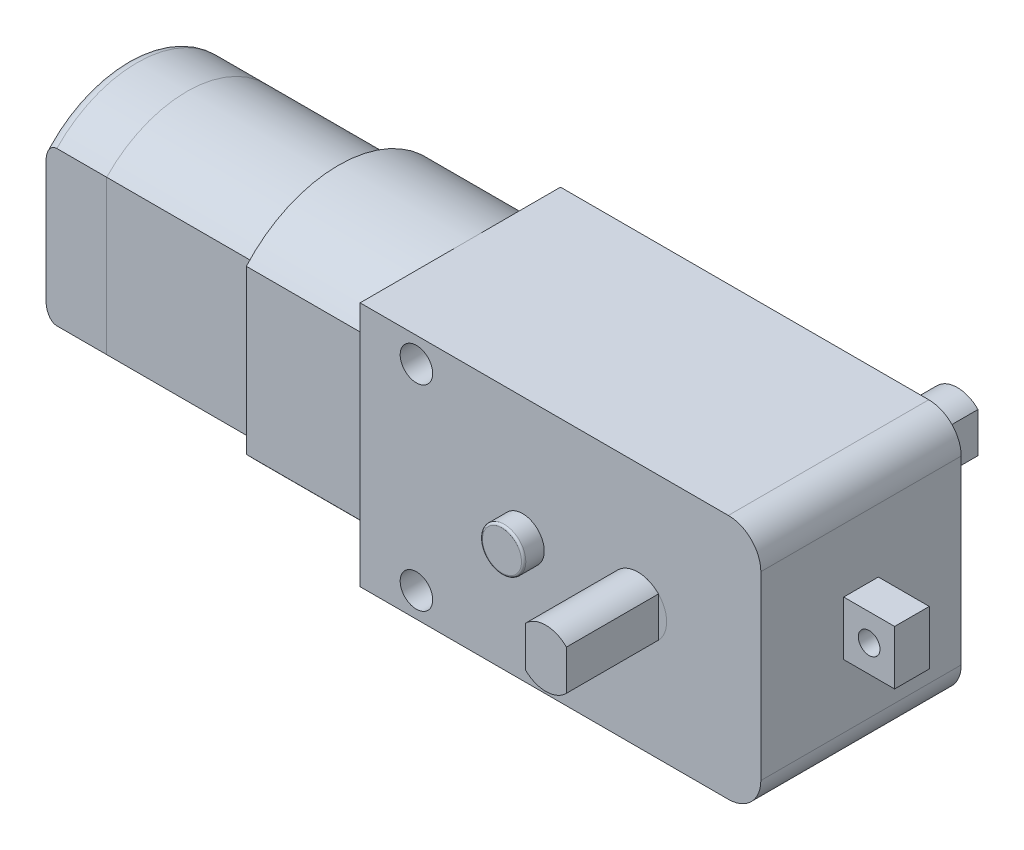
SolidWorks part; units mm, degrees
ref_plane "Alzado" through (0, 0, 0) normal (0, 0, 1) x (1, 0, 0)
ref_plane "Planta" through (0, 0, 0) normal (0, 1, 0) x (1, 0, 0)
ref_plane "Vista lateral" through (0, 0, 0) normal (1, 0, 0) x (0, 0, -1)
sketch "Croquis1" plane through (0, 0, 0) normal (0, 0, 1) x (1, 0, 0)
  line L1 (-18.5, -11.35) -> (15.5, -11.35)
  line L2 (-18.5, -11.35) -> (-18.5, 11.35)
  line L3 (-18.5, 11.35) -> (15.5, 11.35)
  line L4 (18.5, -8.35) -> (18.5, 8.35)
  line L5 (-18.5, -11.35) -> (18.5, 11.35) construction
  line L6 (-18.5, 11.35) -> (18.5, -11.35) construction
  arc A0 (15.5, -11.35) -> (18.5, -8.35) centre (15.5, -8.35) ccw
  arc A1 (15.5, 11.35) -> (18.5, 8.35) centre (15.5, 8.35) cw
  point P0 (0, 0)
  dimension "D3" = 3
  dimension "D1" = 22.7
  dimension "D2" = 37
extrude "Saliente-Extruir1" add sketch "Croquis1" along normal blind 9.25 and the other way blind 9.25
sketch "Croquis2" plane through (-18.5, 0, 0) normal (-1, 0, 0) x (0, 0, 1)
  line L0 (-0.75, -11.35) -> (-0.75, 11.35) construction
  line L1 (7.75, -7.5215) -> (7.75, 7.5215)
  line L2 (-9.25, -7.5215) -> (-9.25, 7.5215)
  line L3 (9.25, 11.35) -> (9.25, -11.35) construction
  line L5 (7.75, -12.1318) -> (7.75, 11.35) construction
  line L6 (-9.25, -12.1318) -> (-9.25, 11.35) construction
  line L7 (-0.75, -12.1318) -> (-0.75, 11.35) construction
  arc A0 (7.75, 7.5215) -> (-9.25, 7.5215) centre (-0.75, 0) ccw
  arc A1 (-9.25, -7.5215) -> (7.75, -7.5215) centre (-0.75, 0) ccw
  point P8 (-0.75, 0)
  dimension "D1" = 22.7
  dimension "D2" = 8.5
  dimension "D3" = 8.5
  dimension "D4" = 1.5
extrude "Saliente-Extruir2" add sketch "Croquis2" along normal blind 12
sketch "Croquis3" plane through (18.5, 0, 0) normal (1, 0, 0) x (0, 0, -1)
  line L1 (1.6, -2.5) -> (-1.6, -2.5)
  line L2 (1.6, -2.5) -> (1.6, 2.5)
  line L3 (1.6, 2.5) -> (-1.6, 2.5)
  line L4 (-1.6, -2.5) -> (-1.6, 2.5)
  line L5 (1.6, -2.5) -> (-1.6, 2.5) construction
  line L6 (1.6, 2.5) -> (-1.6, -2.5) construction
  point P0 (0, 0)
  dimension "D1" = 5
  dimension "D2" = 3.2
extrude "Saliente-Extruir3" add sketch "Croquis3" along normal blind 4.7
sketch "Croquis4" plane through (0, 0, 0) normal (0, 0, 1) x (1, 0, 0)
  line L0 (0, 0) -> (-18.2045, 0) construction
  line L1 (-18.5, -11.35) -> (15.5, -11.35) construction
  line L2 (15.5, 11.35) -> (-18.5, 11.35) construction
  line L3 (-18.5, 11.35) -> (-18.5, -11.35) construction
  circle A0 centre (-13.3, 9.05) radius 1.5
  circle A1 centre (-13.3, -9.05) radius 1.5
  dimension "D1" = 3
  dimension "D2" = 2.3
  dimension "D3" = 2.3
  dimension "D4" = 5.2
  dimension "D5" = 5.2
extrude "Cortar-Extruir1" cut sketch "Croquis4" against normal blind 17.7 and the other way blind 28
sketch "Croquis5" plane through (0, 0, 9.25) normal (0, 0, 1) x (1, 0, 0)
  line L0 (18.5, -8.35) -> (18.5, 8.35) construction
  circle A0 centre (-3.5, 0) radius 2
  point P6 (18.5, 0)
  dimension "D1" = 4
  dimension "D2" = 22
extrude "Saliente-Extruir4" add sketch "Croquis5" along normal blind 1.9
fillet "Redondeo1" radius 0.2 1 edges at (-1.5, 0, 11.15)
sketch "Croquis6" plane through (0, 0, 9.25) normal (0, 0, 1) x (1, 0, 0)
  line L0 (18.5, -8.35) -> (18.5, 8.35) construction
  circle A0 centre (7.15, 0) radius 2.65
  dimension "D1" = 5.3
  dimension "D2" = 11.35
extrude "Cortar-Extruir2" cut sketch "Croquis6" against normal blind 23.9
sketch "Croquis9" plane through (-30.5, 0, 0) normal (-1, 0, 0) x (0, 0, 1)
  line L2 (6.65, -7.5215) -> (6.65, 7.5215)
  line L3 (6.65, -7.0924) -> (6.65, 7.0924)
  line L5 (-8.15, 7.5215) -> (-8.15, -7.5215)
  line L6 (-8.15, 7.0924) -> (-8.15, -7.0924)
  arc A2 (6.9262, 6.7925) -> (-8.4262, 6.7925) centre (-0.75, 0) ccw
  arc A3 (6.65, 7.0924) -> (-8.15, 7.0924) centre (-0.75, 0) ccw
  arc A5 (-8.4262, -6.7925) -> (6.9262, -6.7925) centre (-0.75, 0) ccw
  arc A6 (-8.15, -7.0924) -> (6.65, -7.0924) centre (-0.75, 0) ccw
  dimension "D1" = 1.1
  dimension "D2" = 1.1
  dimension "D3" = 1.1
  dimension "D4" = 1.1
extrude "Saliente-Extruir5" add sketch "Croquis9" along normal blind 14 separate body
sketch "Croquis10" plane through (-44.5, 0, 0) normal (-1, 0, 0) x (0, 0, 1)
  line L0 (-8.15, 7.0924) -> (-8.15, -7.0924)
  line L1 (6.65, 7.0924) -> (6.65, -7.0924)
  line L2 (6.65, -7.0924) -> (6.65, 7.0924) construction
  arc A0 (6.65, 7.0924) -> (-8.15, 7.0924) centre (-0.75, 0) ccw
  arc A1 (6.65, 7.0924) -> (-8.15, 7.0924) centre (-0.75, 0) ccw construction
  arc A2 (-8.15, -7.0924) -> (6.65, -7.0924) centre (-0.75, 0) ccw
extrude "Saliente-Extruir6" add sketch "Croquis10" along normal blind 5.6 separate body
fillet "Redondeo2" radius 1 2 edges at (-50.1, 10.25, -0.75) (-50.1, -10.25, -0.75)
sketch "Croquis11" plane through (-50.1, 0, 0) normal (-1, 0, 0) x (0, 0, 1)
  line L0 (6.65, 5.55) -> (6.65, -7.0924) construction
  line L1 (6.65, -7.0924) -> (6.65, -5.55) construction
  line L2 (2.65, 3.6661) -> (2.65, -3.6661)
  line L3 (2.65, 5.55) -> (2.65, -7.0924) construction
  arc A0 (2.65, 3.6661) -> (2.65, -3.6661) centre (-0.75, 0) ccw
  arc A2 (6.65, 7.0924) -> (-8.15, 7.0924) centre (-0.75, 0) ccw construction
  dimension "D1" = 10
  dimension "D2" = 4
extrude "Saliente-Extruir7" add sketch "Croquis11" along normal blind 2 separate body
sketch "Croquis12" plane through (-52.1, 0, 0) normal (-1, 0, 0) x (0, 0, 1)
  circle A0 centre (-0.75, 0) radius 1
  arc A1 (2.65, 3.6661) -> (2.65, -3.6661) centre (-0.75, 0) ccw construction
  dimension "D1" = 2
extrude "Saliente-Extruir8" add sketch "Croquis12" along normal blind 1 separate body
sketch "Croquis13" plane through (0, 0, -8.15) normal (0, 0, -1) x (-1, 0, 0)
  line L0 (50.1, 5.55) -> (50.1, -5.55) construction
  line L1 (44.5, -4) -> (47.5, -4)
  line L2 (44.5, -4) -> (44.5, 4)
  line L3 (44.5, 4) -> (47.5, 4)
  line L4 (47.5, -4) -> (47.5, 4)
  line L5 (44.5, -4) -> (47.5, 4) construction
  line L6 (44.5, 4) -> (47.5, -4) construction
  line L7 (44.5, 7.0924) -> (44.5, -7.0924) construction
  point P0 (46, 0)
  point P9 (50.1, 0)
  dimension "D1" = 3
  dimension "D2" = 8
extrude "Saliente-Extruir9" add sketch "Croquis13" along normal blind 1.2 separate body
sketch "Croquis14" plane through (0, 0, 1.6) normal (0, 0, 1) x (1, 0, 0)
  line L0 (18.5, 2.5) -> (23.2, -2.5) construction
  line L1 (23.2, 2.5) -> (18.5, -2.5) construction
  circle A0 centre (20.85, 0) radius 1
  dimension "D1" = 2
extrude "Cortar-Extruir3" cut sketch "Croquis14" against normal blind 4.2
sketch "Croquis15" plane through (0, 0, 0) normal (0, 0, 1) x (1, 0, 0)
  line L0 (7.15, -5.2054) -> (7.15, 5.2054) construction
  line L1 (9.05, -1.8473) -> (9.05, 1.8473)
  line L2 (5.25, -1.8473) -> (5.25, 1.8473)
  line L3 (9.05, -5.2054) -> (9.05, 5.2054) construction
  line L4 (5.25, -5.2054) -> (5.25, 5.2054) construction
  arc A0 (5.25, -1.8473) -> (9.05, -1.8473) centre (7.15, 0) ccw
  circle A1 centre (7.15, 0) radius 2.65 construction
  arc A2 (9.05, 1.8473) -> (5.25, 1.8473) centre (7.15, 0) ccw
  point P7 (7.15, 0)
  dimension "D1" = 1.9
  dimension "D2" = 1.9
extrude "Saliente-Extruir10" add sketch "Croquis15" along normal blind 17.75 and the other way blind 20.25 separate body
sketch "Croquis16" plane through (0, 0, 0) normal (0, 0, 1) x (1, 0, 0)
  circle A0 centre (7.15, 0) radius 2.65
  circle A1 centre (7.15, 0) radius 2.65 construction
extrude "Saliente-Extruir11" add sketch "Croquis16" along normal up to surface (9.25 mm away) and the other way blind 12.25 separate body up to face at (9.8, 0, 9.25)
